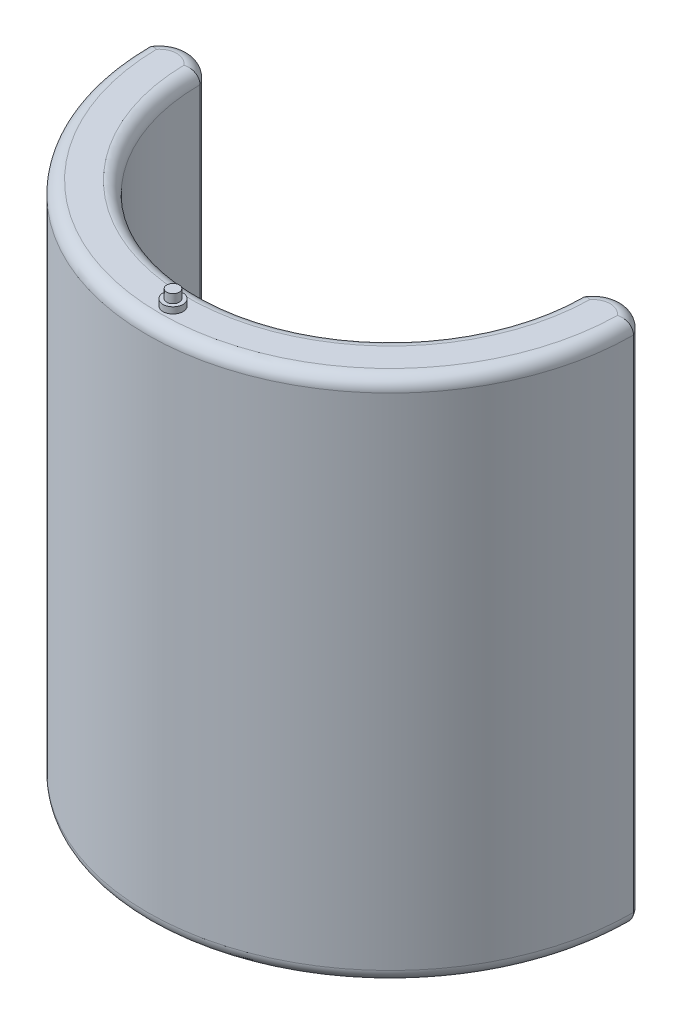
SolidWorks part; units mm, degrees
ref_plane "Front Plane" through (0, 0, 0) normal (0, 0, 1) x (1, 0, 0)
ref_plane "Top Plane" through (0, 0, 0) normal (0, 1, 0) x (1, 0, 0)
ref_plane "Right Plane" through (0, 0, 0) normal (1, 0, 0) x (0, 0, -1)
sketch "Sketch1" plane through (0, 0, 0) normal (0, 1, 0) x (1, 0, 0)
  line L0 (-97.2, 0) -> (-94.2, 0) construction
  line L1 (-79.2, 0) -> (-76.2, 0) construction
  line L3 (79.2, 0) -> (94.2, 0)
  line L5 (-94.2, 0) -> (-79.2, 0) construction
  line L6 (0, 0) -> (0, -15.6906) construction
  arc A0 (-76.2, 0) -> (76.2, 0) centre (0, 0) ccw
  arc A1 (-97.2, 0) -> (97.2, 0) centre (0, 0) ccw
  arc A2 (-79.2, 0) -> (79.2, 0) centre (0, 0) ccw
  arc A3 (-94.2, 0) -> (94.2, 0) centre (0, 0) ccw
  arc A4 (-97.2, 0) -> (-76.2, 0) centre (-86.7, -5.8095) cw
  arc A5 (-94.2, 0) -> (-79.2, 0) centre (-86.7, -4.9749) cw
  arc A6 (94.2, 0) -> (79.2, 0) centre (86.7, -4.9749) ccw
  arc A7 (97.2, 0) -> (76.2, 0) centre (86.7, -5.8095) ccw
  dimension "D2" = 152.4
  dimension "D4" = 12
  dimension "D5" = 9
  dimension "D1" = 3
  dimension "D3" = 15
extrude "Boss-Extrude1" add sketch "Sketch1" along normal mid plane 190
ref_plane "Plane1" through (0, 0, 0) normal (0, 0, 1) x (1, 0, 0)
sketch "Sketch6" plane through (0, -95, 0) normal (0, -1, 0) x (1, 0, 0)
  arc A0 (76.2, 0) -> (97.2, 0) centre (86.7, 5.8095) ccw construction
  arc A1 (76.2, 0) -> (-76.2, 0) centre (0, 0) ccw construction
  arc A2 (-97.2, 0) -> (-76.2, 0) centre (-86.7, 5.8095) ccw construction
  arc A3 (97.2, 0) -> (-97.2, 0) centre (0, 0) ccw construction
  arc A4 (76.2, 0) -> (97.2, 0) centre (86.7, 5.8095) ccw
  arc A5 (76.2, 0) -> (-76.2, 0) centre (0, 0) ccw
  arc A6 (-97.2, 0) -> (-76.2, 0) centre (-86.7, 5.8095) ccw
  arc A7 (97.2, 0) -> (-97.2, 0) centre (0, 0) ccw
extrude "Boss-Extrude2" add sketch "Sketch6" along normal blind 10
fillet "Fillet2" radius 5 4 edges at (-86.7, -105, -6.1905) (0, -105, 97.2) (86.7, -105, -6.1905) (0, -105, 76.2)
mirror "Mirror1" about plane through (0, 0, 0) normal (0, 1, 0) of "Boss-Extrude2", "Fillet2"
ref_plane "Plane3" through (0, 0, 87) normal (0, 0, 1) x (1, 0, 0)
sketch "Sketch9" plane through (0, 0, 87) normal (0, 0, 1) x (1, 0, 0)
  line L0 (92.1884, 105) -> (-92.1884, 105) construction
  line L1 (92.1884, 105) -> (-92.1884, 105) construction
  line L2 (-4, 105) -> (-4, 107.5)
  line L3 (-4, 107.5) -> (-2.5, 107.5)
  line L4 (-2.5, 107.5) -> (-2.5, 111)
  line L5 (-2.5, 111) -> (0, 111)
  line L6 (0, 111) -> (0, 105)
  line L7 (0, 105) -> (-4, 105)
  point P8 (0, 105)
  point P9 (-2.5, 109.25)
  dimension "D1" = 6
  dimension "D2" = 4
  dimension "D3" = 2.5
  dimension "D4" = 2.5
revolve "Revolve1" add sketch "Sketch9" angle 360 about L6
